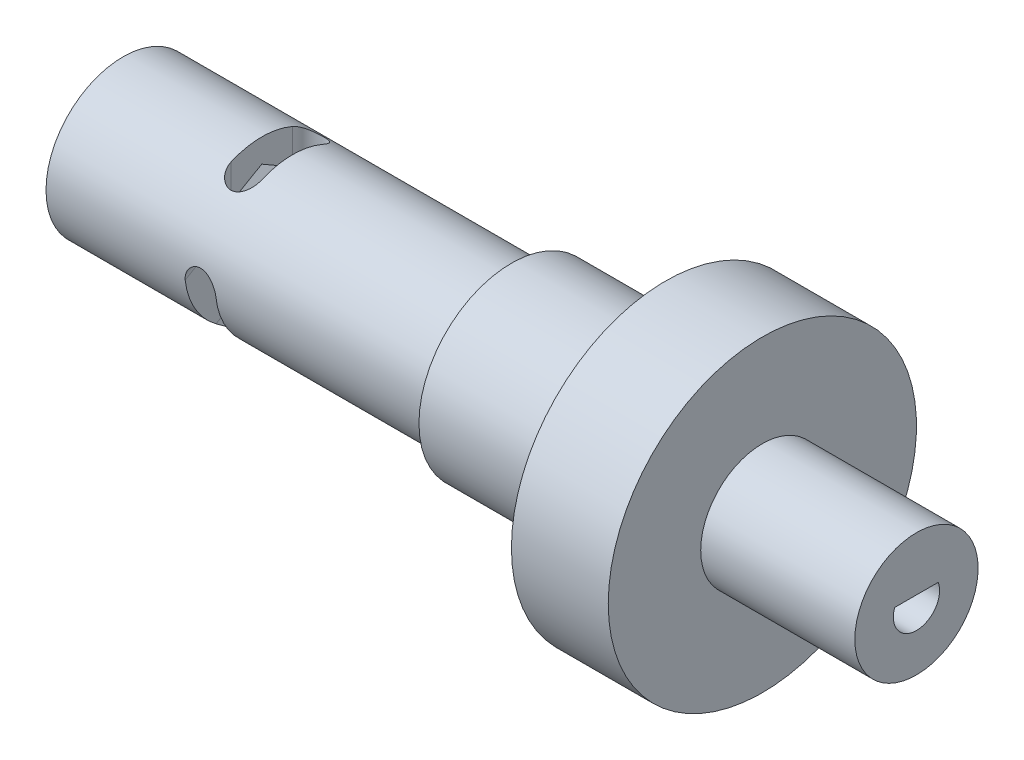
SolidWorks part; units mm, degrees
ref_plane "Front Plane" through (0, 0, 0) normal (0, 0, 1) x (1, 0, 0)
ref_plane "Top Plane" through (0, 0, 0) normal (0, 1, 0) x (1, 0, 0)
ref_plane "Right Plane" through (0, 0, 0) normal (1, 0, 0) x (0, 0, -1)
sketch "Sketch1" plane through (0, 0, 0) normal (0, 0, 1) x (1, 0, 0)
  line L0 (0, 2.5) -> (12.6, 2.5)
  line L1 (17.6, 3) -> (17.6, 5)
  line L2 (17.6, 5) -> (20.7413, 5)
  line L3 (20.7413, 5) -> (20.7413, 2)
  line L4 (20.7413, 2) -> (25.7413, 2)
  line L5 (25.7413, 2) -> (25.7413, 0)
  line L6 (25.7413, 0) -> (0, 0)
  line L7 (0, 0) -> (0, 2.5)
  line L8 (0, 0) -> (44.2194, 0) construction
  line L9 (12.6, 2.5) -> (12.6, 3)
  line L10 (12.6, 3) -> (17.6, 3)
  dimension "D1" = 12.6
  dimension "D2" = 5
  dimension "D3" = 10
  dimension "D4" = 4
  dimension "D5" = 6
  dimension "D6" = 5
  dimension "D7" = 5
revolve "Revolve1" add sketch "Sketch1" angle 360 about L8
cosmetic thread "Cosmetic Thread1" parameters "D1"=3.5, "D2"=4.5
sketch "Sketch2" plane through (0, 0, 0) normal (1, 0, 0) x (0, 0, -1)
  line L1 (0, 1.7321) -> (-1.5, 0.866)
  line L2 (-1.5, 0.866) -> (-1.5, -0.866)
  line L3 (-1.5, -0.866) -> (0, -1.7321)
  line L4 (0, -1.7321) -> (1.5, -0.866)
  line L5 (1.5, -0.866) -> (1.5, 0.866)
  line L6 (1.5, 0.866) -> (0, 1.7321)
  circle A0 centre (0, 0) radius 1.5 construction
  dimension "D1" = 3
extrude "Cut-Extrude1" cut sketch "Sketch2" along normal blind 10
sketch "Sketch3" plane through (0, 0, 0) normal (0, 1, 0) x (1, 0, 0)
  line L0 (0, 0) -> (13.3254, 0) construction
  line L1 (5, 1) -> (5, -1) construction
  line L2 (5.5, 1) -> (5.5, -1)
  line L3 (4.5, 1) -> (4.5, -1)
  line L4 (0, 2.5) -> (0, -2.5) construction
  arc A0 (5.5, 1) -> (4.5, 1) centre (5, 1) ccw
  arc A1 (4.5, -1) -> (5.5, -1) centre (5, -1) ccw
  point P5 (5, 0)
  dimension "D2" = 0.5
  dimension "D1" = 2
  dimension "D3" = 5
extrude "Cut-Extrude2" cut sketch "Sketch3" along normal blind 18
pattern_circular "CirPattern1" count 3 over 360 about axis through (0, 0, 0) along (-1, 0, 0) of "Cut-Extrude2"
sketch "Sketch4" plane through (0, 0, 0) normal (1, 0, 0) x (0, 0, -1)
  line L0 (-0.7071, 0.25) -> (0.7071, 0.25)
  circle A0 centre (0, 0) radius 0.75
  dimension "D1" = 1.5
  dimension "D2" = 0.5
extrude "Cut-Extrude3" cut sketch "Sketch4" against normal offset from surface (48.2587 mm away) 4 from offset 70 contours L0 A0 region at (0, -0.1883, 0) up to face at (25.7413, 0, 2) offset beyond the face yes
ref_axis "Axis1" through (25.7413, 0, 0) along (-1, 0, 0)
ref_plane "Plane1" through (5, 0, 0) normal (-1, 0, 0) x (0, 0, 1)
sketch "Sketch5" plane through (5, 0, 0) normal (-1, 0, 0) x (0, 0, 1)
  line L0 (0, 0) -> (0, 5.3154) construction
  line L1 (0, 0) -> (-4.6033, -2.6577) construction
  line L2 (0, 0) -> (4.6033, -2.6577) construction
